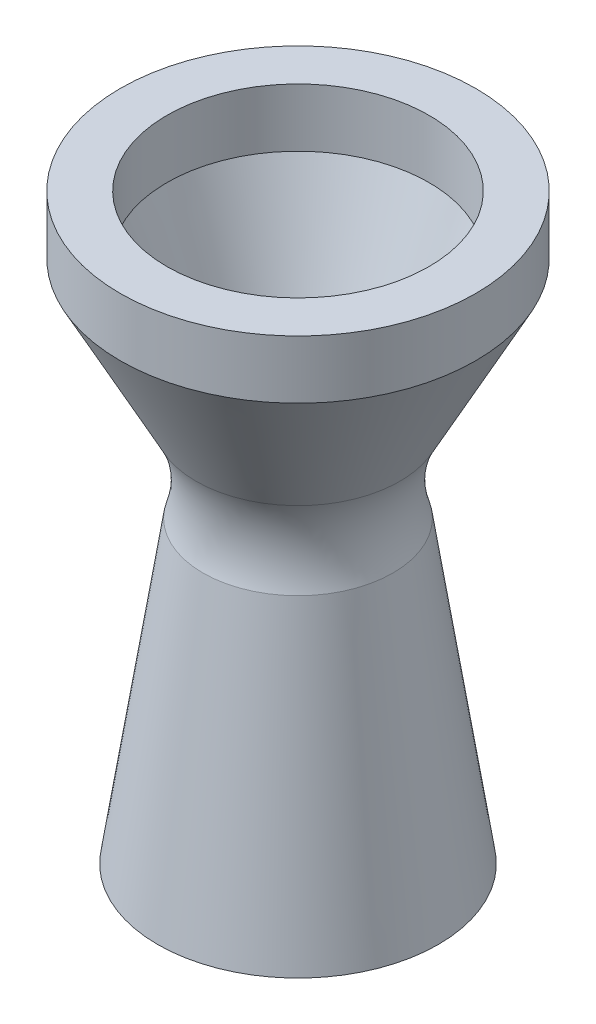
SolidWorks part; units mm, degrees
ref_plane "Front Plane" through (0, 0, 0) normal (0, 0, 1) x (1, 0, 0)
ref_plane "Top Plane" through (0, 0, 0) normal (0, 1, 0) x (1, 0, 0)
ref_plane "Right Plane" through (0, 0, 0) normal (1, 0, 0) x (0, 0, -1)
sketch "Sketch1" plane through (0, 0, 0) normal (0, 1, 0) x (1, 0, 0)
  circle A0 centre (0, 0) radius 22.5
  circle A1 centre (0, 0) radius 30.5
  circle A2 centre (0, 0) radius 32.5 construction
extrude "Boss-Extrude1" add sketch "Sketch1" along normal blind 10
sketch "Sketch2" plane through (0, 0, 0) normal (0, -1, 0) x (1, 0, 0)
  line L0 (22.5, 0) -> (38, 0) construction
  line L1 (0, 0) -> (0, 38) construction
ref_plane "Plane1" through (0, 0, 0) normal (0, 0, 1) x (1, 0, 0)
sketch "Sketch3" plane through (0, 0, 0) normal (0, 0, 1) x (1, 0, 0)
  line L0 (-30.5, 0) -> (-17.4895, -24.4271)
  line L1 (-16.3187, -38.6361) -> (-24.083, -90)
  line L2 (-12.8208, -24.7805) -> (-22.5, 0)
  line L3 (-24.083, -90) -> (-20.583, -90)
  line L4 (-20.583, -90) -> (-11.6608, -35.834)
  line L6 (-22.5, 0) -> (-30.5, 0)
  line L7 (0, 0) -> (0, 43.8983) construction
  arc A0 (-16.3187, -38.6361) -> (-17.4895, -24.4271) centre (-33.3765, -32.8889) ccw
  arc A1 (-11.6608, -35.834) -> (-12.8208, -24.7805) centre (-32.3816, -32.4209) ccw
  dimension "D1" = 18
  dimension "D2" = 21
  dimension "D3" = 90
  dimension "D4" = 3.5
revolve "Revolve1" add sketch "Sketch3" angle 360 about L7
